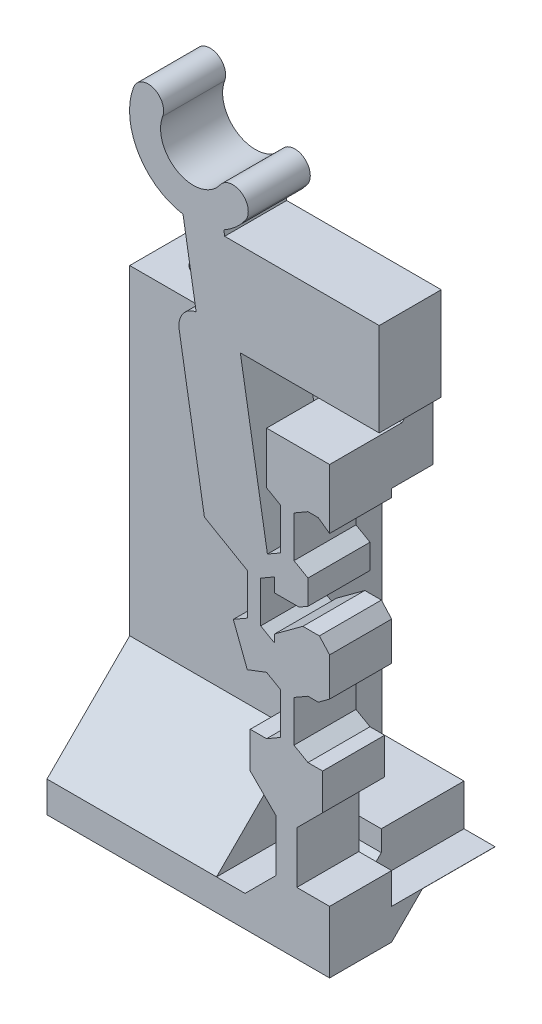
SolidWorks part; units mm, degrees
material "Nylon 6/12"
ref_plane "Front Plane" through (0, 0, 0) normal (0, 0, 1) x (1, 0, 0)
ref_plane "Top Plane" through (0, 0, 0) normal (0, 1, 0) x (1, 0, 0)
ref_plane "Right Plane" through (0, 0, 0) normal (1, 0, 0) x (0, 0, -1)
sketch "Sketch-SkeletonConfigUp" plane through (0, 0, 0) normal (0, 0, 1) x (1, 0, 0)
  line L0 (0, 0) -> (0, -50000) construction
  line L1 (0, 0) -> (4.5811, 6.2164) construction
  line L2 (9.8143, 13.3177) -> (4.5811, 13.945) construction
  line L3 (4.5811, 13.945) -> (2.9713, 10.4094) construction
  line L4 (2.9713, 10.4094) -> (4.5811, 6.2164) construction
  line L5 (4.5811, 13.945) -> (6.2429, 19.1409) construction
  line L6 (2.9713, 10.4094) -> (0.0405, 27.8193) construction
  line L7 (4.5811, 6.2164) -> (9.8143, 13.3177) construction
  line L8 (-587.3593, -797.0242) -> (9.8143, 13.3177) construction
  dimension "D2" = 7.7221
  dimension "D3" = 8.8212
  dimension "D4" = 5.2707
  dimension "D5" = 119.553
  dimension "D6" = 3.8848
  dimension "D7" = 5.4552
  dimension "D8" = 17.6549
  dimension "D9" = 4.4914
  dimension "D10" = 6.745
  dimension "D11" = 145.964
  dimension "D12" = 143.612
sketch "Sketch-SkeletonConfigDown" plane through (0, 0, 0) normal (0, 0, 1) x (1, 0, 0)
  line L0 (0, 0) -> (0, -50000) construction
  line L1 (0, 0) -> (4.5811, 6.2164) construction
  line L2 (9.8143, 13.3177) -> (4.5811, 13.945) construction
  line L3 (4.5811, 13.945) -> (6.1909, 10.4094) construction
  line L4 (6.1909, 10.4094) -> (4.5811, 6.2164) construction
  line L5 (4.5811, 13.945) -> (1.753, 18.6098) construction
  line L6 (6.1909, 10.4094) -> (-8.8652, 19.6294) construction
  line L7 (4.5811, 6.2164) -> (9.8143, 13.3177) construction
  line L8 (-589.9357, -800.5203) -> (9.8143, 13.3177) construction
  dimension "D2" = 7.7221
  dimension "D3" = 8.8212
  dimension "D4" = 5.2707
  dimension "D5" = 119.553
  dimension "D6" = 3.8848
  dimension "D7" = 5.4552
  dimension "D8" = 17.6549
  dimension "D9" = 4.4914
  dimension "D10" = 6.745
  dimension "D11" = 145.964
  dimension "D1" = 143.612
ref_plane "Plane-Cam Base" through (9.128, 0, 0) normal (1, 0, 0) x (0, 0, -1)
ref_plane "Plane-Down-to-Up Derailleur Clearance" through (6.628, 0, 0) normal (1, 0, 0) x (0, 0, -1)
ref_plane "Plane-Cam Cavity Roof" through (5.128, 0, 0) normal (1, 0, 0) x (0, 0, -1)
sketch "Sketch-SwitchBossUp" plane through (0, 0, 0) normal (0, 0, 1) x (1, 0, 0)
  line L0 (3.5811, 11.4759) -> (3.5811, 12.945) construction
  line L5 (5.5811, 12.5549) -> (5.5811, 11.3705)
  line L7 (1.5115, 25.1048) -> (1.5536, 24.8548)
  line L8 (-0.4607, 24.7728) -> (1.6966, 11.9577) construction
  line L9 (2.9713, 10.4094) -> (0.0405, 27.8193) construction
  line L11 (0.1364, 21.2256) -> (2.1086, 21.5576) construction
  line L15 (6.628, -23.7286) -> (6.628, 23.7286) construction
  line L16 (2.9713, 10.4094) -> (4.5811, 6.2164) construction
  line L17 (3.5811, 12.945) -> (3.5811, 14.945) construction
  line L18 (5.5811, 12.945) -> (5.5811, 14.945) construction
  line L19 (4.2561, 13.945) -> (4.9061, 13.945) construction
  line L20 (3.5811, 14.945) -> (5.5811, 14.945) construction
  line L21 (3.5811, 12.945) -> (5.5811, 12.945) construction
  line L22 (4.5811, 12.945) -> (4.5811, 14.945) construction
  line L23 (4.5811, 6.2164) -> (8.5404, 7.1023) construction
  line L24 (1.9713, 9.4094) -> (1.9713, 11.4094) construction
  line L25 (3.9713, 9.4094) -> (3.9713, 11.4094) construction
  line L26 (3.9713, 9.4094) -> (1.9713, 9.4094) construction
  line L27 (1.9713, 11.4094) -> (3.9713, 11.4094) construction
  line L28 (3.5811, 7.2164) -> (5.5811, 7.2164) construction
  line L29 (3.5811, 7.2164) -> (3.5811, 5.2164) construction
  line L30 (5.5811, 7.2164) -> (5.5811, 5.2164) construction
  line L31 (3.5811, 5.2164) -> (5.5811, 5.2164) construction
  line L32 (4.9061, 6.2164) -> (4.2561, 6.2164) construction
  line L40 (3.2963, 10.4094) -> (2.6463, 10.4094) construction
  line L66 (0.0405, 27.8193) -> (0.0405, 50027.8193) construction
  line L75 (4.5811, 3.3049) -> (4.5405, -0.6733) construction
  line L76 (5.5811, 11.3705) -> (5.5811, 12.5549) construction
  line L81 (9.1185, 1033.2334) -> (9.1185, 20.05) construction
  line L85 (6.9307, 9.5241) -> (9.1185, 7.0942) construction
  line L88 (5.7256, 17.835) -> (6.628, 17.835)
  line L92 (3.7762, 8.3129) -> (6.9307, 9.5241) construction
  line L101 (4.5811, 6.2164) -> (6.9307, 9.5241) construction
  line L103 (0.0405, 27.8193) -> (1.9448, 26.4638) construction
  line L104 (6.9307, 9.5241) -> (9.1185, 7.0942) construction
  line L107 (1.9713, 9.4094) -> (1.9713, 9.0197) construction
  line L109 (0.0405, 27.8193) -> (-2.1498, 28.6358) construction
  line L111 (6.628, 9.8603) -> (6.628, 8.0076)
  line L112 (6.628, 9.8603) -> (6.9307, 9.5241) construction
  line L114 (7.3693, 7.7363) -> (7.3563, 7.7363) construction
  line L121 (5.0405, -1.6882) -> (5.0405, -0.6733) construction
  line L122 (9.028, 22.3548) -> (9.028, 20.3548)
  line L127 (5.5811, 15.3347) -> (5.5811, 14.945) construction
  line L133 (2.9713, 10.4094) -> (6.1909, 10.4094) construction
  line L134 (4.5811, 10.4094) -> (4.5811, 13.945) construction
  line L135 (4.5811, 10.4094) -> (4.5811, 6.2164) construction
  line L137 (3.9713, 9.4094) -> (5.5811, 7.2164) construction
  line L139 (5.3335, 10.4094) -> (3.9713, 9.4094)
  line L142 (2.5405, -2.1733) -> (2.5405, -3.6733)
  line L143 (9.1185, 20.05) -> (9.1185, 18.3248) construction
  line L145 (9.1185, 16.5986) -> (9.1185, -49992.4252) construction
  line L147 (5.5811, 11.3705) -> (5.5811, 12.5549) construction
  line L150 (2.5405, -3.6733) -> (6.628, -3.6733)
  line L151 (4.0405, 1.8267) -> (5.0405, 1.8267) construction
  line L152 (4.2555, 14.945) -> (4.2555, 12.945)
  line L153 (4.9055, 14.945) -> (4.9055, 12.945)
  line L157 (3.5811, 17.835) -> (3.5811, 15.335)
  line L162 (3.2963, 11.4094) -> (3.2963, 9.4094)
  line L164 (2.6463, 11.4094) -> (2.6463, 9.4094)
  line L169 (4.2561, 7.2164) -> (4.2561, 5.2164)
  line L170 (4.9061, 5.2164) -> (4.9061, 7.2164)
  line L175 (4.2561, 7.2164) -> (3.5811, 7.6061)
  line L176 (4.9061, 7.2164) -> (5.5811, 7.6061)
  line L177 (5.5811, 7.2164) -> (5.5811, 7.6061) construction
  line L179 (4.2561, 5.2164) -> (3.5811, 4.8267)
  line L180 (3.5811, 5.2164) -> (3.5811, 4.8267) construction
  line L181 (3.5811, 4.8267) -> (2.7905, 4.8267)
  line L183 (4.9061, 5.2164) -> (5.5811, 4.8267)
  line L184 (5.5811, 5.2164) -> (5.5811, 4.8267) construction
  line L186 (9.128, -23.7286) -> (9.128, 23.7286) construction
  line L187 (2.6463, 9.4094) -> (1.9713, 9.0197)
  line L188 (3.2963, 9.4094) -> (3.9713, 9.0197)
  line L189 (3.2963, 11.4094) -> (3.9713, 11.7991)
  line L190 (2.6463, 11.4094) -> (1.6966, 11.9577)
  line L191 (3.9713, 11.4094) -> (3.9713, 11.7991) construction
  line L192 (3.9713, 11.7991) -> (3.9713, 11.1241)
  line L193 (4.9055, 12.945) -> (5.5811, 12.5549)
  line L194 (4.2555, 12.945) -> (3.6202, 12.5782)
  line L195 (3.9713, 11.1241) -> (5.1543, 11.1241)
  line L196 (3.9713, 9.4094) -> (3.9713, 9.0197)
  line L197 (3.5811, 7.2164) -> (3.5811, 7.6061) construction
  line L199 (3.5811, 7.6061) -> (2.6469, 7.2496)
  line L201 (2.7905, 3.0767) -> (2.7905, 4.8267)
  line L202 (2.7905, 3.0767) -> (6.2905, 3.0767) construction
  line L207 (9.1185, 18.3248) -> (9.1185, 16.5986) construction
  line L208 (6.628, -3.6733) -> (6.628, -0.6733)
  line L209 (9.1185, 20.05) -> (9.1185, 16.5986) construction
  line L211 (5.0405, -0.6733) -> (5.0405, 1.8267)
  line L212 (4.0405, -0.6733) -> (4.0405, 1.8267)
  line L214 (4.2555, 14.945) -> (3.5798, 15.335)
  line L215 (3.5798, 15.335) -> (3.5811, 15.335)
  line L216 (4.9055, 14.945) -> (5.5811, 15.335)
  line L217 (5.5811, 12.945) -> (5.5811, 12.5549) construction
  line L218 (4.9055, 14.945) -> (4.9055, 15.335) construction
  line L219 (5.5811, 15.335) -> (3.5798, 15.335) construction
  line L221 (9.028, 22.3548) -> (9.028, 24.8548)
  line L224 (3.5811, 17.835) -> (5.7256, 17.835)
  line L232 (6.628, 14.945) -> (6.628, 17.835)
  line L236 (1.5536, 24.8548) -> (9.028, 24.8548)
  line L250 (9.028, 20.3548) -> (2.3111, 20.3548)
  line L254 (5.0405, -0.6733) -> (4.0405, -0.6733) construction
  line L255 (4.0405, -0.6733) -> (3.0345, -0.6733) construction
  line L256 (4.5811, 6.2164) -> (4.5811, 3.3049) construction
  line L259 (5.0405, -0.6733) -> (6.628, -0.6733)
  line L261 (1.6966, 11.9577) -> (0.5733, 12.6062)
  line L262 (0.5733, 12.6062) -> (-0.6452, 19.8444)
  line L263 (4.0405, 1.8267) -> (2.7905, 3.0767)
  line L266 (5.0405, 1.8267) -> (6.2905, 3.0767)
  line L270 (2.5405, -2.1733) -> (4.0405, -0.6733)
  line L279 (0.175, 20.9965) -> (-0.4607, 24.7728)
  line L283 (2.3111, 20.3548) -> (3.6202, 12.5782)
  line L367 (5.5811, 4.8267) -> (6.2905, 4.8267)
  line L368 (6.2905, 4.8267) -> (6.2905, 3.0767)
  line L471 (2.6469, 7.2496) -> (1.9713, 9.0197)
  line L472 (6.1335, 10.4094) -> (6.628, 9.8603)
  line L473 (5.3335, 10.4094) -> (6.1335, 10.4094)
  line L474 (5.5811, 7.6061) -> (6.0811, 7.6061)
  line L475 (6.0811, 7.6061) -> (6.628, 8.0076)
  line L477 (5.1543, 11.1241) -> (5.5811, 11.3705)
  line L478 (5.5811, 15.335) -> (6.0811, 15.335)
  line L479 (5.5811, 14.945) -> (6.9307, 14.945) construction
  line L480 (6.628, 14.945) -> (6.0811, 15.335)
  arc A0 (1.5115, 25.1048) -> (2.5558, 26.0289) centre (0.0405, 27.8193) ccw
  arc A1 (-1.5413, 25.1678) -> (-2.8525, 28.8978) centre (0.0405, 27.8193) cw
  arc A2 (-2.8525, 28.8978) -> (-1.447, 28.3738) centre (-2.1498, 28.6358) cw
  arc A3 (2.5558, 26.0289) -> (1.3338, 26.8987) centre (1.9448, 26.4638) ccw
  arc A4 (-1.447, 28.3738) -> (1.3338, 26.8987) centre (0.0405, 27.8193) ccw
  arc A5 (3.5811, 12.945) -> (3.5811, 14.945) centre (3.1778, 13.945) ccw construction
  arc A6 (5.5811, 12.945) -> (5.5811, 14.945) centre (5.9843, 13.945) cw construction
  arc A7 (2.528, 9.9183) -> (1.9713, 11.4094) centre (1.568, 10.4094) ccw construction
  arc A8 (3.9713, 11.4094) -> (3.9713, 9.4094) centre (4.3745, 10.4094) ccw construction
  arc A9 (3.5811, 7.2164) -> (3.5811, 5.2164) centre (3.1779, 6.2164) cw construction
  arc A10 (5.5811, 7.2164) -> (5.5811, 5.2164) centre (5.9844, 6.2164) ccw construction
  circle A28 centre (0.0405, 27.8193) radius 2.3375 construction
  arc A29 (1.9713, 9.4094) -> (2.528, 9.9183) centre (1.568, 10.4094) ccw construction
  arc A38 (-0.6452, 19.8444) -> (0.175, 20.9965) centre (0.341, 20.0104) cw
  arc A39 (-1.5413, 25.1678) -> (-0.4607, 24.7728) centre (0.0405, 27.8193) ccw
  point P7 (0, 0)
  point P53 (4.5811, 13.945)
  point P63 (2.9713, 10.4094)
  point P72 (2.5405, 26.0289)
  point P93 (1.1225, 21.3916)
  dimension "D23" = 1.5875
  dimension "D24" = 0.75
  dimension "D2" = 2
  dimension "D5" = 2
  dimension "D16" = 42
  dimension "D27" = 120
  dimension "D28" = 120
  dimension "D29" = 120
  dimension "D30" = 120
  dimension "D31" = 120
  dimension "D32" = 120
  dimension "D33" = 120
  dimension "D34" = 120
  dimension "D21" = 2.5
  dimension "D38" = 2
  dimension "D42" = 45
  dimension "D43" = 120
  dimension "D15" = 0.25
  dimension "D6" = 0.65
  dimension "D12" = 1
  dimension "D19" = 0.65
  dimension "D20" = 1
  dimension "D18" = 1.5
  dimension "D36" = 3
  dimension "D37" = 2.5
  dimension "D44" = 5
  dimension "D73" = 2.5
  dimension "D10" = 45
  dimension "D74" = 3.5
  dimension "D75" = 3
  dimension "D76" = 1
  dimension "D8" = 42
  dimension "D39" = 0.8
  dimension "D40" = 0.5
  dimension "D41" = 0.675
  dimension "D77" = 1.183
  dimension "D25" = 120
  dimension "D26" = 120
  dimension "D78" = 120
  dimension "D35" = 120
  dimension "D79" = 0.5
extrude "Boss-Switch Body" add sketch "Sketch-SwitchBossUp" along normal blind 3
sketch "Sketch1" plane through (0, 0, 0) normal (0, 0, -1) x (-1, 0, 0)
  line L1 (-6.628, -3.6733) -> (-2.5405, -3.6733)
  line L2 (-6.628, -3.6733) -> (-6.628, -2.1733)
  line L4 (-2.5405, -3.6733) -> (-2.5405, -2.1733)
  line L5 (-3.5811, 18.835) -> (-6.628, 18.835)
  line L10 (-6.628, 18.835) -> (-6.628, 15.335)
  line L12 (-6.628, 15.335) -> (-3.5811, 15.335)
  line L13 (-6.628, -2.1733) -> (-2.5405, -2.1733)
  line L14 (-3.5811, 15.335) -> (-3.5811, 18.835)
  line L22 (-2.5405, -3.6733) -> (-6.628, -3.6733) construction
  line L25 (-6.628, -3.6733) -> (-6.628, -0.6733) construction
  point P1 (0, 0)
  point P4 (-6.628, -2.1733)
  point P5 (-5.0405, -0.6733)
  point P9 (-2.4163, -1.5452)
  point P10 (-2.5405, -2.1733)
  point P11 (-1.5536, -2.1733)
  point P14 (-4.6594, 18.6648)
  point P18 (-2.5405, -2.2044)
  point P19 (-6.6675, -0.6733)
  point P21 (-3.5811, 18.835)
  point P24 (-3.4446, -0.6733)
  point P25 (-3.61, -2.1733)
  point P26 (-5.0405, -2.1733)
  dimension "D1" = 3.5
extrude "Boss-Flange Width" add sketch "Sketch1" along normal blind 5
ref_plane "Plane-Sta2Sit Groove" through (0.0405, 0, 0) normal (1, 0, 0) x (0, 0, -1)
ref_plane "Plane-Cam Outer Surface" through (-12.0395, 0, 0) normal (1, 0, 0) x (0, 0, -1)
ref_plane "Plane-FlangeTop" through (-7.0395, 0, 0) normal (1, 0, 0) x (0, 0, -1)
sketch "Sketch2" plane through (-7.0395, 0, 0) normal (1, 0, 0) x (0, 0, -1)
  line L0 (5, 15.335) -> (0, 15.335) construction
  line L1 (5, 17.335) -> (1, 17.335)
  line L2 (5, 17.335) -> (5, 15.335)
  line L3 (5, 15.335) -> (1, 15.335)
  line L4 (1, 17.335) -> (1, 15.335)
  line L5 (-3, -3.6733) -> (-3, -0.6733) construction
  line L12 (5, -2.1733) -> (5, -3.6733)
  line L13 (5, -3.6733) -> (-3, -3.6733)
  line L14 (-3, -2.1733) -> (-3, -3.6733)
  line L15 (0, 10.4094) -> (0, 27.8193) construction
  line L16 (1, 15.335) -> (1, -0.6733) construction
  line L22 (5, -2.1733) -> (0, -2.1733) construction
  line L23 (5, -2.1733) -> (-3, -2.1733)
  point P9 (0, 0)
  point P10 (5, -2.1733)
  dimension "D1" = 1
  dimension "D2" = 2
  dimension "D3" = 16.0083
extrude "Boss-Flange Height" add sketch "Sketch2" along normal up to surface (10.6206 mm away) up to face at (3.5811, 17.0493, -0.5714)
sketch "Sketch10" plane through (0, 15.335, 0) normal (0, 1, 0) x (1, 0, 0)
  line L0 (9.128, -23.7286) -> (9.128, 23.7286) construction
  line L1 (6.628, 5) -> (5.128, 5)
  line L2 (6.628, 5) -> (6.628, 2)
  line L3 (6.628, 2) -> (5.128, 2)
  line L5 (4.628, 7) -> (4.628, 0.64) construction
  line L6 (3.5811, 1) -> (-7.0395, 1) construction
  line L8 (5.128, 5) -> (5.128, 2)
  point P1 (4.628, 0.64)
  dimension "D1" = 1
  dimension "D2" = 0.5
  dimension "D3" = 4.5
extrude "Cut-Up-To-Down Derailleur Clearance" cut sketch "Sketch10" along normal up to next
sketch "Sketch17" plane through (0, 15.335, 0) normal (0, -1, 0) x (1, 0, 0)
  line L0 (5.128, -5) -> (-7.0395, -5)
  line L1 (5.128, -5) -> (-7.0395, -5) construction
  line L2 (-7.0395, -5) -> (-7.0395, -1)
  line L3 (-7.0395, -1) -> (5.128, -1)
  line L4 (5.128, -1) -> (5.128, -5)
  line L5 (-7.0395, -1) -> (-7.0395, -5) construction
  line L6 (5.128, -5) -> (5.128, -2) construction
extrude "Boss-Flange Support" add sketch "Sketch17" along normal up to surface (17.5083 mm away) up to face at (0.7096, -2.1733, -0.6667)
sketch "Sketch-HolePositions" plane through (0, -3.6733, 0) normal (0, -1, 0) x (1, 0, 0)
  line L0 (-7.0395, -3) -> (6.628, -3) construction
  line L1 (6.628, -5) -> (-7.0395, -5) construction
  line L2 (6.628, -5) -> (6.628, 3) construction
  line L4 (-7.0395, -22.2167) -> (-7.0395, 22.2167) construction
  point P6 (-5.0395, -3)
  point P7 (-0.5395, -3)
  dimension "D1" = 2
  dimension "D2" = 4.5
  dimension "D3" = 2
sketch "Sketch6" plane through (0, -3.6733, 0) normal (0, -1, 0) x (-1, 0, 0)
  point P0 (5.0395, 3)
  point P3 (0.5395, 3)
hole_wizard "Tap Drill for M2x0.4 Tap1" positions "Sketch6" profile "Sketch5" hole size "M2x0.4" standard "ANSI Metric" end condition through all
sketch "Sketch5" plane through (-5.0395, -3.6733, -3) normal (1, 0, 0) x (0, 0, -1)
  line L0 (0, 0) -> (0, 33.0591)
  line L1 (0, 33.0591) -> (0.8, 33.0591)
  line L2 (0.8, 33.0591) -> (0.8, 0)
  line L5 (0.8, 0) -> (0, 0)
  line L11 (0, -6.35) -> (0, 107.95) construction
  dimension "Thru Hole Dia." = 1.6
  dimension "Thru Hole Depth" = 33.0591
sketch "Sketch9" plane through (0, -3.6733, 0) normal (0, -1, 0) x (1, 0, 0)
  point P0 (-5.0395, -3)
  point P3 (-0.5395, -3)
hole_wizard "M2 Clearance Hole2" positions "Sketch9" profile "Sketch8" hole size "M2" standard "ANSI Metric"
sketch "Sketch8" plane through (-5.0395, -3.6733, -3) normal (1, 0, 0) x (0, 0, -1)
  line L0 (0, 0) -> (0, 15.721)
  line L1 (0, 15.721) -> (1.2, 15)
  line L2 (1.2, 15) -> (1.2, 0)
  line L5 (1.2, 0) -> (0, 0)
  line L10 (0, 15.721) -> (-1.2, 15) construction
  line L11 (0, -6.35) -> (0, 107.95) construction
  dimension "Hole Dia." = 2.4
  dimension "Hole Depth" = 15
  dimension "Drill Angle" = 118
sketch "Sketch-Measurements for Derailleur Ramps" [suppressed] plane through (0, 0, 0) normal (0, 0, 1) x (1, 0, 0)
  line L0 (3.184, 15.1695) -> (2.4687, 19.4188)
  line L1 (2.8264, 17.2941) -> (1.8402, 17.1281)
  line L2 (2.9713, 10.4094) -> (0.0405, 27.8193) construction
  line L3 (1.8402, 17.1281) -> (-1.3081, 15.0016)
  line L4 (6.1909, 10.4094) -> (-8.8652, 19.6294) construction
  line L5 (1.8402, 17.1281) -> (2.6012, 12.6077)
  line L6 (2.6012, 12.6077) -> (-1.3081, 15.0016)
  line L7 (0.2661, 16.0649) -> (0.2661, 17.1281)
  line L8 (0.2661, 17.1281) -> (1.8402, 17.1281)
  line L9 (6.1909, 10.4094) -> (2.9713, 10.4094)
  line L10 (5.386, 8.3129) -> (3.7762, 8.3129)
  line L11 (2.6116, 18.5698) -> (1.5115, 25.1048) construction
  line L12 (6.1909, 10.4094) -> (4.5811, 6.2164) construction
  line L13 (4.5811, 8.3129) -> (4.5811, 8.7912)
  line L14 (4.5811, 6.2164) -> (5.386, 8.3129)
  line L15 (2.9713, 10.4094) -> (4.5811, 6.2164) construction
  line L16 (3.7762, 8.3129) -> (4.5811, 6.2164)
  line L17 (5.386, 8.3129) -> (5.386, 8.7912)
  dimension "D1" = 1.5742
  dimension "D2" = 0.8049
ref_plane "Plane1" through (0, 7.1023, 0) normal (0, 1, 0) x (1, 0, 0)
ref_plane "Plane-Cantilever Cut" [suppressed] through (7.0848, 8.5204, -1.9058) normal (-0.6301, -0.7578, 0.1695) x (-0.7765, 0.6151, -0.1368)
sketch "Sketch14" [suppressed] plane through (7.0848, 8.5204, -1.9058) normal (-0.6301, -0.7578, 0.1695) x (-0.7765, 0.6151, -0.1368)
  line L0 (2.3023, -1.6911) -> (-0.3551, -1.6911)
  line L2 (2.3023, -4.3362) -> (2.3023, -1.6911)
  line L3 (-0.3551, -1.6911) -> (-0.3551, -4.4608)
  line L5 (-0.3551, -4.4608) -> (1.0087, -5.0843)
  line L6 (1.0087, -5.0843) -> (2.3023, -4.3362)
extrude "Cut-Down-to-Up Cantilever Slope" [suppressed] cut sketch "Sketch14" against normal up to next
ref_plane "Plane-Symmetry Plane" through (0, 0, 1.5) normal (0, 0, 1) x (1, 0, 0)
sketch "Sketch-Cable Center Point" plane through (0, 0, 1.5) normal (0, 0, 1) x (1, 0, 0)
  line L0 (0.0405, 27.8193) -> (0.1722, 27.0366)
  line L1 (2.9713, 10.4094) -> (0.0405, 27.8193) construction
  point P0 (0.0405, 27.8193)
  dimension "D1" = 0.7937
chamfer "Chamfer-Flange Support" distance 1.5 angle 45 1 edges at (3.5811, 17.335, -3)
chamfer "Chamfer-Flange Support 2" distance 1.5 angle 45 2 edges at (5.128, 17.085, -2) (5.128, 15.335, -1.5)
chamfer "Chamfer7" [suppressed] distance 1 angle 45
sketch "Sketch23" plane through (0, 0, -1) normal (0, 0, 1) x (1, 0, 0)
  line L0 (8.5102, -0.1733) -> (1.1605, -0.1733)
  line L2 (1.1605, -0.1733) -> (1.1605, 15.335)
  line L3 (1.1605, 15.335) -> (8.5102, 15.335)
  line L4 (8.5102, 15.335) -> (8.5102, -0.1733)
  line L5 (0.6605, -3.6733) -> (0.6605, 11.3267) construction
  line L8 (5.5811, 15.335) -> (3.5811, 15.335) construction
  line L11 (2.5405, -2.1733) -> (-7.0395, -2.1733) construction
  point P4 (1.1605, -0.6733)
  point P9 (5.128, -0.6733)
  point P11 (5.128, 15.3039)
  point P12 (5.128, -0.6733)
  point P14 (8.5102, -0.6733)
  point P17 (0, 0)
  dimension "D1" = 0.5
  dimension "D2" = 2
extrude "Cut-Gap for Printing" cut sketch "Sketch23" against normal through all
sketch "Sketch27" plane through (5.128, 0, 0) normal (1, 0, 0) x (0, 0, -1)
  line L0 (3.5, 18.835) -> (3.5, 15.335) construction
  line L1 (2.5, 18.835) -> (5, 18.835)
  line L2 (2.5, 18.835) -> (2.5, 15.335)
  line L3 (2.5, 15.335) -> (5, 15.335)
  line L4 (5, 18.835) -> (5, 15.335)
  line L5 (5, 18.835) -> (5, 15.335) construction
  line L6 (2, 18.835) -> (3.5, 18.835) construction
  line L8 (5, 15.335) -> (3.5, 15.335) construction
  point P4 (5, 18.835)
  point P10 (2.5, 18.835)
  point P13 (2.5, 13.835)
  dimension "D1" = 1
extrude "Cut-Wide Derailleur Clearance" cut sketch "Sketch27" against normal blind 4 and the other way through all
chamfer "Chamfer9" distance 1.25 angle 45 1 edges at (4.8545, 18.835, -2.5)
sketch "Sketch28" plane through (0, 0, -1) normal (0, 0, 1) x (1, 0, 0)
  line L0 (3.5811, 18.835) -> (6.628, 18.835)
  line L1 (6.628, 18.835) -> (6.628, 17.835)
  line L2 (6.628, 17.835) -> (3.5811, 17.835)
  line L3 (3.5811, 17.835) -> (3.5811, 18.835)
extrude "Cut-Extrude1" cut sketch "Sketch28" along normal up to surface (1 mm away) up to face at (5.1045, 18.335, 0)
chamfer "Chamfer10" distance 0.5 angle 45 2 edges at (5.1045, 17.835, -1) (3.5811, 16.585, -1)
chamfer "Chamfer-Flange Support 3" distance 1 angle 45 1 edges at (-0.9558, -2.1733, -1)
sketch "Sketch31" plane through (-7.0395, 0, 0) normal (-1, 0, 0) x (0, 0, 1)
  line L0 (-5, -2.1807) -> (-5, -3.6733)
  line L1 (-5, -3.6733) -> (-5, 17.335) construction
  line L2 (-5, -3.6733) -> (0, -3.6733)
  line L3 (0, 200000) -> (0, -250000) construction
  line L4 (3, -3.6733) -> (-5, -3.6733) construction
  line L5 (0, -3.6733) -> (-1.4926, -2.1807)
  line L7 (-1.4926, -2.1807) -> (-5, -2.1807)
  line L8 (0, -2.1733) -> (-1, -1.1733) construction
  point P5 (-1.8675, -2.0408)
  point P16 (-2.1655, -1.5078)
  point P17 (-2.5023, -1.1807)
  point P18 (-2.491, -1.1807)
  point P19 (-2.7708, -0.9025)
  dimension "D1" = 30
extrude "Cut-Extrude2" cut sketch "Sketch31" against normal through all
sketch "Sketch32" plane through (-7.0395, 0, 0) normal (-1, 0, 0) x (0, 0, 1)
  line L0 (3, -2.1733) -> (-1, 1.8267)
  line L1 (-1, 17.335) -> (-1, -1.1733) construction
  line L2 (-1, 1.8267) -> (-1, -2.0828)
  line L3 (-1, -2.0828) -> (0.4063, -3.3555)
  line L4 (0.4063, -3.3555) -> (3, -3.3555)
  line L5 (3, -2.1733) -> (3, -3.6733) construction
  line L6 (3, -3.3555) -> (3, -2.1733)
  line L7 (3, -2.1733) -> (0, -2.1733) construction
  dimension "D1" = 45
extrude "Boss-Extrude2" add sketch "Sketch32" against normal up to surface (8.2 mm away) up to face at (1.1605, 9.1317, -2.9)
equation "\"axle-diameter\"=2"
equation "\"switch-thickness\"=12"
equation "\"base-width\"=4.0"
equation "\"axle-bushing-radius\"=3"
equation "\"clearance\"= 0.25"
equation "\"arm-width\"=1.5"
equation "\"min-diameter\"=70"
equation "\"alpha\"=143.6120"
equation "\"gamma\"=119.5526"
equation "\"delta\"=145.9637"
equation "\"epsilon\"=6.7452"
equation "\"l_AB\"=8.8212"
equation "\"l_AC\"=4.4914"
equation "\"l_BD\"=5.2707"
equation "\"l_CD\"=3.8848"
equation "\"l_CE\"=17.6549"
equation "\"l_DF\"=5.4552"
equation "\"l_OA\"=7.7221"
equation "\"D2@Sketch-SkeletonConfigUp\" = \"l_OA\""
equation "\"D3@Sketch-SkeletonConfigUp\" = \"l_AB\""
equation "\"D4@Sketch-SkeletonConfigUp\" = \"l_BD\""
equation "\"D5@Sketch-SkeletonConfigUp\" = \"gamma\""
equation "\"D6@Sketch-SkeletonConfigUp\" = \"l_CD\""
equation "\"D7@Sketch-SkeletonConfigUp\" = \"l_DF\""
equation "\"D8@Sketch-SkeletonConfigUp\" = \"l_CE\""
equation "\"D9@Sketch-SkeletonConfigUp\" = \"l_AC\""
equation "\"D_groove\"=3.175"
equation "\"D7@Sketch-SkeletonConfigDown\" = \"l_DF\""
equation "\"D6@Sketch-SkeletonConfigDown\" = \"l_CD\""
equation "\"D2@Sketch-SkeletonConfigDown\" = \"l_OA\""
equation "\"D3@Sketch-SkeletonConfigDown\" = \"l_AB\""
equation "\"D9@Sketch-SkeletonConfigDown\" = \"l_AC\""
equation "\"D8@Sketch-SkeletonConfigDown\" = \"l_CE\""
equation "\"D5@Sketch-SkeletonConfigDown\" = \"gamma\""
equation "\"D4@Sketch-SkeletonConfigDown\" = \"l_BD\""
equation "\"D1@Sketch-SkeletonConfigDown\" = \"alpha\""
equation "\"hinge_length\"=1.5"
equation "\"hinge_depth\"=0.25"
equation "\"D10@Sketch-SkeletonConfigUp\"=\"epsilon\""
equation "\"D11@Sketch-SkeletonConfigUp\"=\"delta\""
equation "\"D12@Sketch-SkeletonConfigUp\"=\"alpha\""
equation "\"D11@Sketch-SkeletonConfigDown\"=\"delta\""
equation "\"D10@Sketch-SkeletonConfigDown\"=\"epsilon\""
equation "\"EE_dx\"=8.9056"
equation "\"EE_dy\"=8.1898"
equation "\"r_groove\"=\"D_groove\"/2"
equation "\"t_wall\"=25.4/16"
equation "\"width_lower\"=\"D_groove\"+\"t_wall\""
equation "\"cable_to_bottom\"=30.6257"
equation "\"switch_EE-up_base_dy\"=24"
equation "\"switch_EE-down_base_dy\"=16"
equation "\"D_axle\"=25.4/8"
equation "\"D_up_to_down\"=16"
equation "\"D_down_to_up\"=25"
equation "\"t_cam_base\"=7.5"
equation "\"D23@Sketch-SwitchBossUp\"=\"D_groove\"/2"
equation "\"D1@Sketch-Cable Center Point\"=\"D_groove\"/4"
